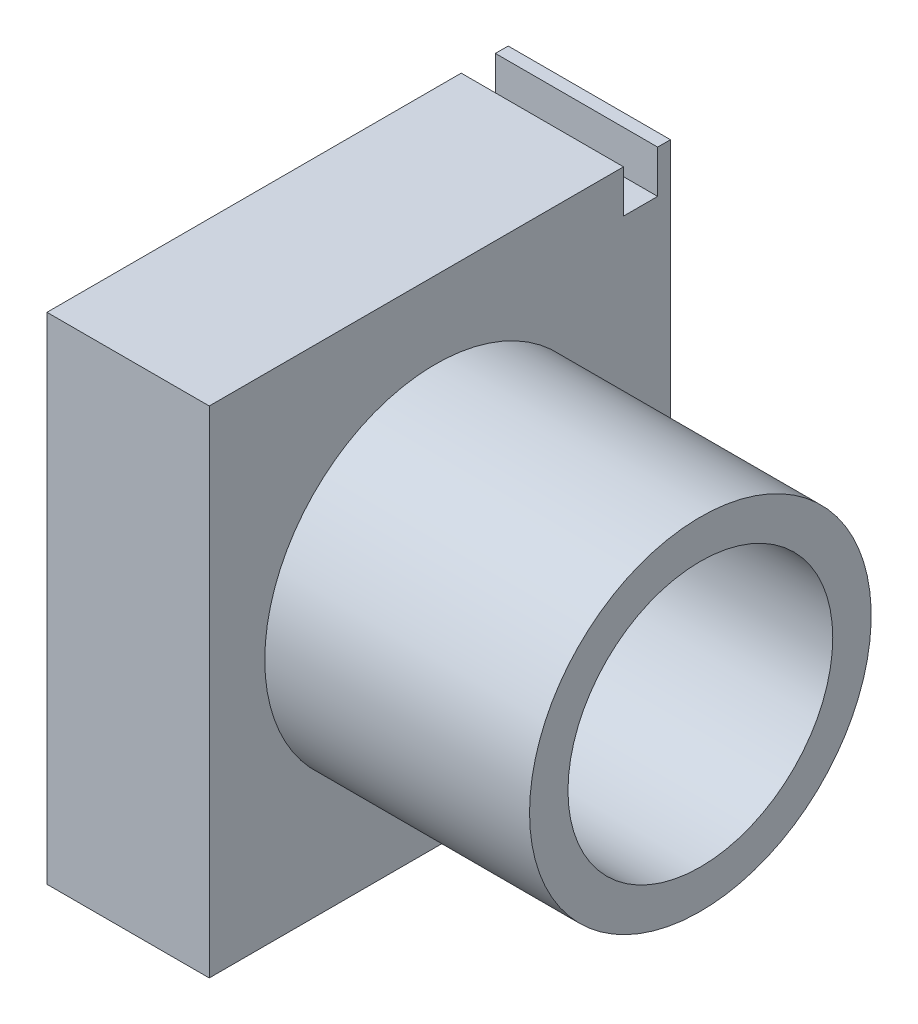
SolidWorks part; units mm, degrees
note: The reader was unsure of these and kept them because the rebuilt part matched: shared geometry of "Sketch2<3>".
ref_plane "Front Plane" through (0, 0, 0) normal (0, 0, 1) x (1, 0, 0)
ref_plane "Top Plane" through (0, 0, 0) normal (0, 1, 0) x (1, 0, 0)
ref_plane "Right Plane" through (0, 0, 0) normal (1, 0, 0) x (0, 0, -1)
sketch "Sketch1" plane through (0, 0, 0) normal (0, 0, 1) x (1, 0, 0)
  line L0 (0, 0) -> (0, 58)
  line L1 (0, 58) -> (19, 58)
  line L2 (19, 58) -> (19, 0)
  line L3 (19, 0) -> (0, 0)
  dimension "D1" = 58
  dimension "D2" = 19
extrude "Boss-Extrude1" add sketch "Sketch1" along normal blind 54
sketch "Sketch2" plane through (0, 0, 0) normal (-1, 0, 0) x (0, 0, 1)
  line L0 (0, 29) -> (27.5, 29)
  line L1 (0, 58) -> (0, 0) construction
  line L2 (27.5, 29) -> (54, 29)
  line L3 (54, 58) -> (54, 0) construction
  circle A0 centre (9.25, 29) radius 1.9
  circle A1 centre (45.75, 29) radius 1.9
  circle A2 centre (27.5, 29) radius 20
  circle A3 centre (27.5, 29) radius 15.5
  dimension "D4" = 3.8
  dimension "D5" = 3.8
  dimension "D6" = 31
  dimension "D7" = 40
  dimension "D1" = 27.5
  dimension "D2" = 18.25
  dimension "D3" = 18.25
extrude "Boss-Extrude2" add sketch "Sketch2<3>" against normal blind 50 contours A3 L0 A0 A2 A1 L2 | A1 A2 L2 | L2 A2 A1 | A3 L2 A1 A2 A0 L0 | A0 A2 L0 | L0 A2 A0
sketch "Sketch2<3>" plane through (0, 0, 0) normal (-1, 0, 0) x (0, 0, 1) same geometry as "Sketch2"
extrude "Cut-Extrude1" cut sketch "Sketch2" against normal blind 10 contours L0 A0 | L0 A0 | L2 A1 | L2 A1 | A2 L0 A0 | A2 A0 L0 | A2 A1 L2 | A2 L2 A1
fillet "Fillet1" radius 10 1 edges at (9.5, 0, 0)
sketch "Sketch3" plane through (0, 0, 0) normal (1, 0, 0) x (0, 0, -1)
  line L0 (0, 0) -> (0, 57)
  line L1 (0, 57) -> (0, 67)
  line L2 (0, 67) -> (-5, 67)
  line L3 (-5, 67) -> (-5, 0)
  line L4 (-54, 0) -> (-10, 0) construction
  line L5 (-5, 0) -> (0, 0)
  dimension "D1" = 57
  dimension "D2" = 5
  dimension "D3" = 10
extrude "Boss-Extrude3" add sketch "Sketch3" against normal blind 50
sketch "Sketch4" plane through (0, 0, 0) normal (0, 0, -1) x (-1, 0, 0)
  line L0 (0, 0) -> (0, 57)
  line L1 (0, 67) -> (0, 0) construction
  line L2 (0, 57) -> (14, 57)
  line L3 (0, 53) -> (50, 53)
  line L4 (50, 0) -> (50, 67) construction
  line L5 (50, 53) -> (50, 0)
  line L6 (50, 0) -> (0, 0)
  line L7 (17, 53) -> (17, 67)
  line L8 (50, 67) -> (0, 67) construction
  line L9 (17, 67) -> (50, 67)
  line L10 (50, 67) -> (50, 53)
  circle A0 centre (14, 57) radius 1.25
  circle A1 centre (14, 63.5) radius 1.25
  dimension "D2" = 2.5
  dimension "D3" = 2.5
  dimension "D1" = 57
  dimension "D4" = 6.5
  dimension "D5" = 14
  dimension "D6" = 53
  dimension "D7" = 3
extrude "Cut-Extrude2" cut sketch "Sketch4" against normal through all
sketch "Sketch5" plane through (0, 0, 0) normal (0, 0, -1) x (-1, 0, 0)
  line L0 (0, 67) -> (0, 53)
  line L1 (0, 53) -> (17, 53)
  line L2 (17, 53) -> (17, 67)
  line L3 (17, 67) -> (0, 67)
extrude "Cut-Extrude3" cut sketch "Sketch5" against normal blind 2
sketch "Sketch6" plane through (0, 58, 0) normal (0, 1, 0) x (1, 0, 0)
  line L0 (0, -5.5) -> (0, -1.5)
  line L1 (0, -54) -> (0, -5) construction
  line L2 (0, -5) -> (0, 0) construction
  line L3 (0, -1.5) -> (19, -1.5)
  line L4 (19, -54) -> (19, 0) construction
  line L5 (19, -1.5) -> (19, -5.5)
  line L6 (19, -47.5) -> (19, -7.5) construction
  line L7 (19, -5.5) -> (0, -5.5)
  line L8 (-17, -5) -> (0, -5) construction
  line L9 (-17, -2) -> (0, -2) construction
  dimension "D1" = 0.5
  dimension "D2" = 0.5
extrude "Cut-Extrude4" cut sketch "Sketch6" against normal up to surface (5 mm away) up to face at (-8.5, 53, 3.5)
sketch "Sketch7" plane through (0, 0, 2) normal (0, 0, -1) x (-1, 0, 0)
  line L0 (0, 67) -> (0, 53)
  line L1 (0, 53) -> (17, 53)
  line L2 (17, 53) -> (17, 67)
  line L3 (17, 67) -> (0, 67)
extrude "Cut-Extrude5" cut sketch "Sketch7" against normal through all
